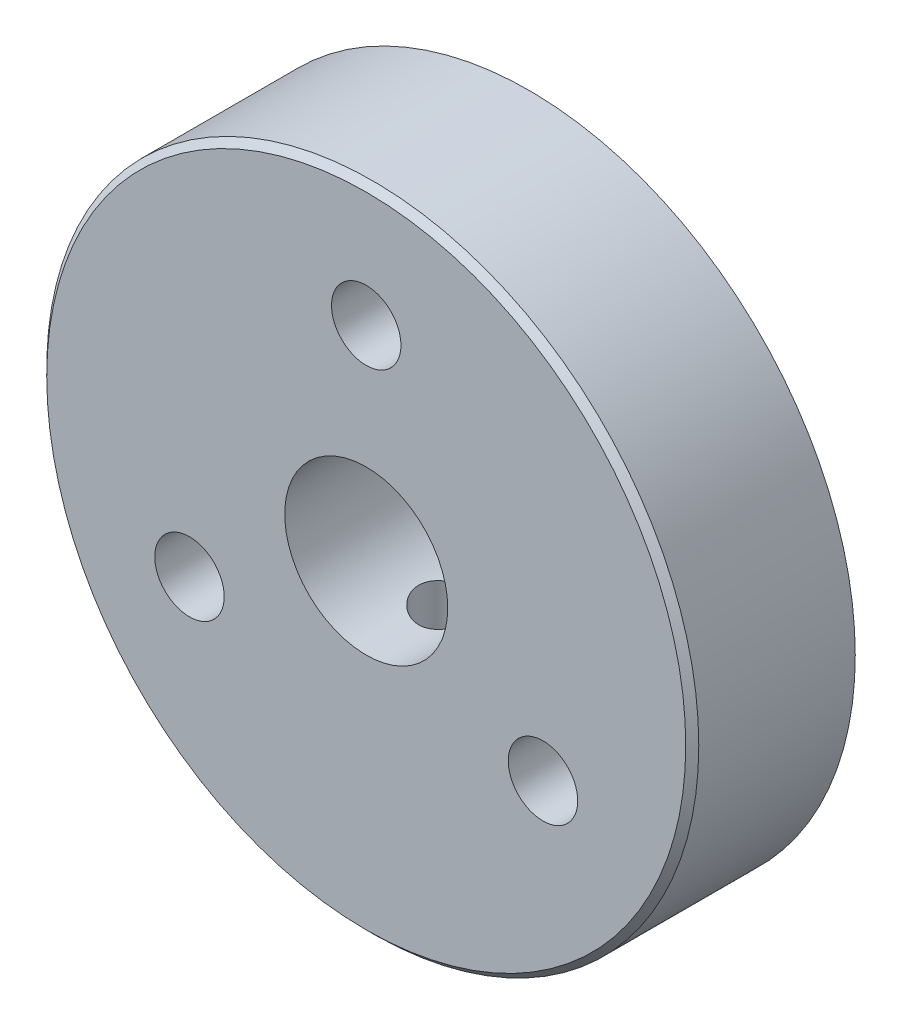
SolidWorks part; units mm, degrees
material "6061-T6 (SS)"
ref_plane "Front Plane" through (0, 0, 0) normal (0, 0, 1) x (1, 0, 0)
ref_plane "Top Plane" through (0, 0, 0) normal (0, 1, 0) x (1, 0, 0)
ref_plane "Right Plane" through (0, 0, 0) normal (1, 0, 0) x (0, 0, -1)
sketch "Sketch2" plane through (0, 0, 0) normal (0, 0, 1) x (1, 0, 0)
  circle A0 centre (0, 0) radius 12.7
  circle A1 centre (0, 0) radius 3.175
  dimension "D1" = 25.4
  dimension "D2" = 6.35
  dimension "D3" = 9.525
extrude "Boss-Extrude1" add sketch "Sketch2" along normal mid plane 6.35
chamfer "Chamfer1" distance 0.254 angle 45 1 edges at (12.7, 0, 3.175)
hole_wizard "#6-32 Tapped Hole1" positions "Sketch3" profile "Sketch4" tap size "#6-32" standard "ANSI Inch" end condition through all
sketch "Sketch3" plane through (0, 0, 3.175) normal (0, 0, 1) x (1, 0, 0)
  line L0 (0, 0) -> (0, 7.9502) construction
  line L3 (3.4925, 0) -> (-3.4925, 0) construction
  circle A2 centre (0, 0) radius 7.9502 construction
  point P0 (0, 7.9502)
  point P9 (6.8851, -3.9751)
  point P10 (-6.8851, -3.9751)
  dimension "D1" = 7.9502
  dimension "D3" = 90
  dimension "D2" = 3
sketch "Sketch4" plane through (0, 7.9502, 3.175) normal (1, 0, 0) x (0, -1, 0)
  line L0 (0, 0) -> (0, 6.35)
  line L1 (0, 6.35) -> (1.3525, 6.35)
  line L2 (1.3525, 6.35) -> (1.3525, 0)
  line L5 (1.3525, 0) -> (0, 0)
  line L11 (0, -6.35) -> (0, 107.95) construction
  dimension "Thru Tap Drill Dia." = 2.7051
  dimension "Thru Tap Drill Depth" = 6.35
cosmetic thread "Hole Thread4"
cosmetic thread "Hole Thread5"
cosmetic thread "Hole Thread6"
ref_plane "Plane1" through (0, -12.7, 0) normal (0, -1, 0) x (-1, 0, 0)
hole_wizard "#4-40 Tapped Hole2" positions "Sketch9" profile "Sketch10" tap size "#4-40" standard "ANSI Inch" end condition up to next
sketch "Sketch9" plane through (0, -12.7, 0) normal (0, -1, 0) x (-1, 0, 0)
  point P0 (0, 0)
sketch "Sketch10" plane through (0, -12.7, 0) normal (1, 0, 0) x (0, 0, -1)
  line L0 (0, 0) -> (0, 9.525)
  line L1 (0, 9.525) -> (1.1303, 9.525)
  line L2 (1.1303, 9.525) -> (1.1303, 0.3945)
  line L3 (1.1303, 0.3945) -> (1.4732, 0)
  line L5 (1.4732, 0) -> (0, 0)
  line L6 (-1.1303, 0.3945) -> (-1.4732, 0) construction
  line L11 (0, -6.35) -> (0, 107.95) construction
  dimension "Thru Tap Drill Dia." = 2.2606
  dimension "Thru Tap Drill Depth" = 9.525
  dimension "Near C'Sink Dia." = 2.9464
  dimension "Near C'Sink Angle" = 82
cosmetic thread "Hole Thread3"
